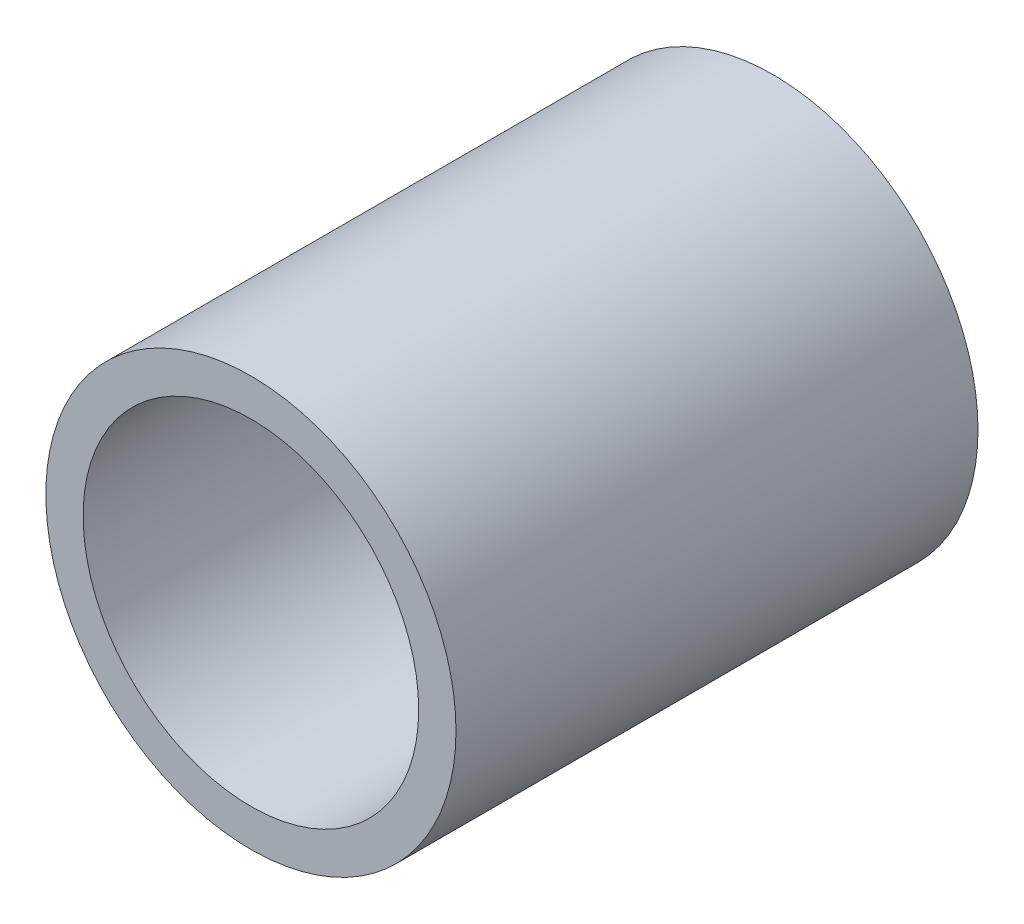
SolidWorks part; units mm, degrees
ref_plane "Top" through (0, 0, 0) normal (0, 0, 1) x (1, 0, 0)
ref_plane "Front" through (0, 0, 0) normal (0, 1, 0) x (1, 0, 0)
ref_plane "Right" through (0, 0, 0) normal (1, 0, 0) x (0, 0, -1)
sketch "Body Sketch" plane through (0, 0, 0) normal (0, 0, 1) x (1, 0, 0)
  circle A0 centre (0, 0) radius 4.5
  circle A1 centre (0, 0) radius 5.5
  dimension "D1" = 9
  dimension "D2" = 1
extrude "Body Extrude" add sketch "Body Sketch" along normal blind 14
